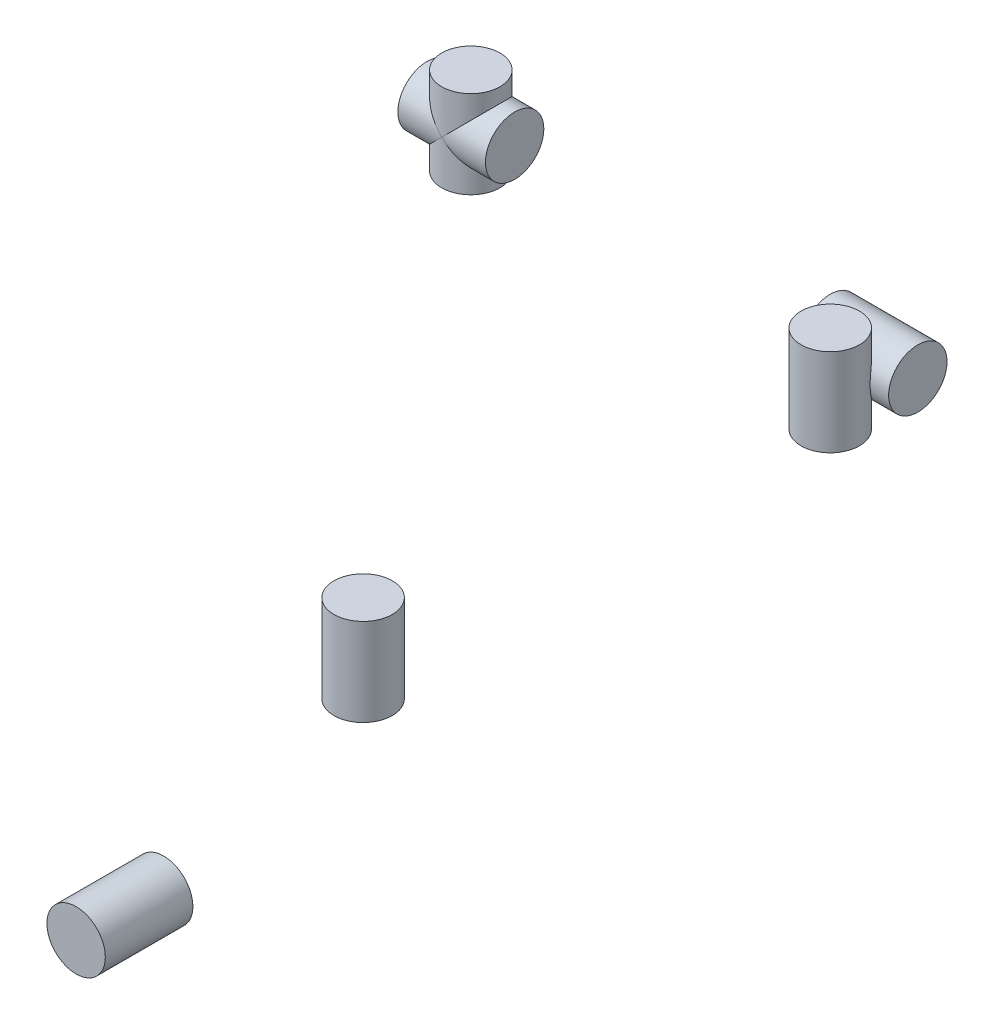
SolidWorks part; units mm, degrees
ref_plane "Front Plane" through (0, 0, 0) normal (0, 0, 1) x (1, 0, 0)
ref_plane "Top Plane" through (0, 0, 0) normal (0, 1, 0) x (1, 0, 0)
ref_plane "Right Plane" through (0, 0, 0) normal (1, 0, 0) x (0, 0, -1)
sketch "Sketch1" plane through (0, 0, 0) normal (0, 1, 0) x (1, 0, 0)
  line L0 (0, 0) -> (0, 135.8) construction
  line L1 (0, 135.8) -> (-37.5, 135.8) construction
  line L2 (-37.5, 135.8) -> (-37.5, 295.8) construction
  line L3 (-37.5, 295.8) -> (-37.5, 310.8) construction
  line L4 (-37.5, 310.8) -> (-175.6, 310.8) construction
  line L5 (-175.6, 310.8) -> (-203.8, 310.8) construction
  dimension "D1" = 135.8
  dimension "D2" = 160
  dimension "D3" = 15
  dimension "D4" = 37.5
  dimension "D5" = 138.1
  dimension "D6" = 28.2
sketch "Sketch2" plane through (0, 0, 0) normal (0, 0, 1) x (1, 0, 0)
  circle A0 centre (0, 0) radius 10
  dimension "D1" = 20
extrude "Boss-Extrude1" add sketch "Sketch2" against normal blind 30
sketch "Sketch4" plane through (0, 0, 0) normal (0, 1, 0) x (1, 0, 0)
  circle A0 centre (-37.5, 135.8) radius 10
  circle A1 centre (-37.5, 295.8) radius 10
  circle A2 centre (-175.6, 310.8) radius 10
  dimension "D1" = 20
  dimension "D2" = 20
  dimension "D3" = 20
extrude "Boss-Extrude3" add sketch "Sketch4" along normal blind 15 and the other way blind 15 separate body
ref_plane "Plane1" through (-37.5, 0, 0) normal (1, 0, 0) x (0, 0, -1)
sketch "Sketch5" plane through (-37.5, 0, 0) normal (1, 0, 0) x (0, 0, -1)
  line L0 (295.8, 0) -> (310.8, 0) construction
  circle A0 centre (310.8, 0) radius 10
  dimension "D1" = 20
extrude "Boss-Extrude4" add sketch "Sketch5" along normal blind 15 and the other way blind 15
ref_plane "Plane2" through (-175.6, 0, 0) normal (1, 0, 0) x (0, 0, -1)
sketch "Sketch6" plane through (-175.6, 0, 0) normal (1, 0, 0) x (0, 0, -1)
  circle A0 centre (310.8, 0) radius 10
extrude "Boss-Extrude5" add sketch "Sketch6" along normal blind 15 and the other way blind 15
